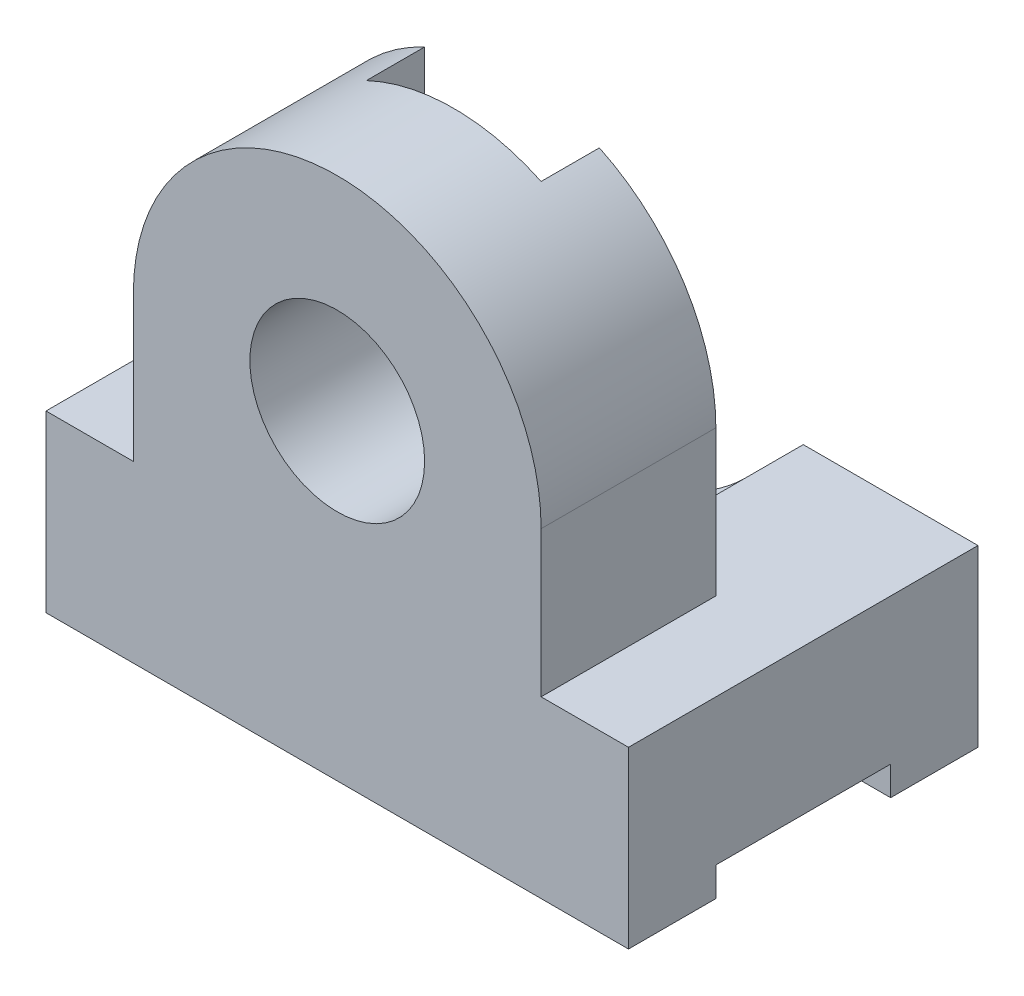
SolidWorks part; units mm, degrees
ref_plane "Front Plane" through (0, 0, 0) normal (0, 0, 1) x (1, 0, 0)
ref_plane "Top Plane" through (0, 0, 0) normal (0, 1, 0) x (1, 0, 0)
ref_plane "Right Plane" through (0, 0, 0) normal (1, 0, 0) x (0, 0, -1)
sketch "Sketch1" plane through (0, 0, 0) normal (0, 0, 1) x (1, 0, 0)
  line L0 (-50, -15) -> (50, -15)
  line L1 (-50, -15) -> (-50, 15)
  line L2 (50, -15) -> (50, 15)
  line L3 (-50, 15) -> (50, 15)
  line L4 (-50, -15) -> (50, 15) construction
  line L5 (50, -15) -> (-50, 15) construction
  line L10 (-13.125, -15) -> (35, 40) construction
  line L11 (-35, 40) -> (13.125, -15) construction
  line L12 (35, 15) -> (35, 40)
  line L13 (-35, 15) -> (-35, 40)
  line L19 (-20, 15) -> (20, 15)
  line L20 (-20, 15) -> (-20, 5)
  line L21 (-20, 5) -> (20, 5)
  line L22 (20, 15) -> (20, 5)
  arc A0 (35, 40) -> (-35, 40) centre (0, 40) ccw
  circle A1 centre (0, 40) radius 15
  point P1 (0, 0)
  point P2 (0, 0)
  point P18 (0, 15)
  point P19 (0, 15)
  dimension "D5" = 35
  dimension "D7" = 30
  dimension "D1" = 100
  dimension "D2" = 30
  dimension "D3" = 10
  dimension "D4" = 55
  dimension "D6" = 40
extrude "Boss-Extrude1" add sketch "Sketch1" against normal blind 60 contours L3 L22 L21 L20 L1 L0 L2 | L22 L3 L20 L21 region at (0, -1.5385, 0) region at (0, 10, 0)
extrude "Boss-Extrude2" add sketch "Sketch1<3>" against normal blind 30 contours L12 A0 L13 L3 region at (-34.078, 27.5, 0)
sketch "Sketch1<3>" plane through (0, 0, 0) normal (0, 0, 1) x (1, 0, 0) same geometry as "Sketch1"
extrude "Cut-Extrude1" cut sketch "Sketch1<4>" against normal through all from offset 40 contours L22 L3 L20 L21 region at (0, 10, 0) offset against normal yes
sketch "Sketch1<4>" plane through (0, 0, 0) normal (0, 0, 1) x (1, 0, 0) same geometry as "Sketch1"
sketch "Sketch2" plane through (50, 0, 0) normal (1, 0, 0) x (0, 0, -1)
  line L0 (15, -20) -> (45, -20)
  line L1 (15, -20) -> (15, -10)
  line L2 (45, -20) -> (45, -10)
  line L3 (15, -10) -> (45, -10)
  line L4 (15, -20) -> (45, -10) construction
  line L5 (45, -20) -> (15, -10) construction
  line L6 (60, -15) -> (0, -15) construction
  point P0 (45, -15)
  point P1 (30, -15)
  point P8 (30, -15)
  dimension "D1" = 30
  dimension "D2" = 5
extrude "Cut-Extrude2" cut sketch "Sketch2" against normal through all
sketch "Sketch3" plane through (0, 0, -30) normal (0, 0, -1) x (-1, 0, 0)
  line L0 (15, 40) -> (15, 85.0339)
  line L1 (-15, 40) -> (-15, 85.0339)
  line L2 (-15, 85.0339) -> (15, 85.0339)
  arc A0 (-15, 40) -> (15, 40) centre (0, 40) ccw
  dimension "D1" = 30
extrude "Cut-Extrude3" cut sketch "Sketch3" against normal blind 10
sketch "Sketch4" plane through (0, 5, 0) normal (0, 1, 0) x (1, 0, 0)
  line L0 (-20, 60) -> (20, 60) construction
  circle A0 centre (0, 60) radius 10
  dimension "D1" = 20
extrude "Cut-Extrude4" cut sketch "Sketch4" against normal through all
